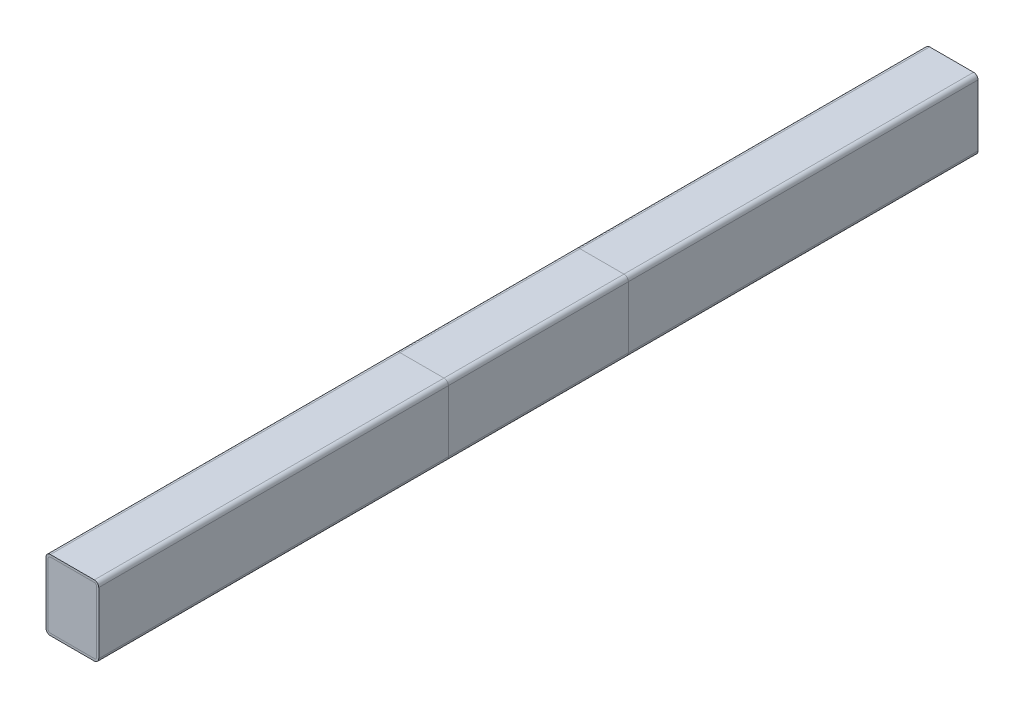
SolidWorks part; units mm, degrees
material "Plain Carbon Steel"
ref_plane "Front Plane" through (0, 0, 0) normal (0, 0, 1) x (1, 0, 0)
ref_plane "Top Plane" through (0, 0, 0) normal (0, 1, 0) x (1, 0, 0)
ref_plane "Right Plane" through (0, 0, 0) normal (1, 0, 0) x (0, 0, -1)
sketch "Sketch4" plane through (0, 0, 0) normal (0, 0, 1) x (1, 0, 0)
  line L4 (31.75, -47.6907) -> (-31.75, -47.6907)
  line L5 (34.925, 44.3843) -> (34.925, -44.5157)
  line L6 (-34.925, -44.5157) -> (-34.925, 44.3843)
  line L7 (-31.75, 47.5593) -> (31.75, 47.5593)
  line L8 (31.75, -50.8657) -> (-31.75, -50.8657)
  line L9 (38.1, 44.3843) -> (38.1, -44.5157)
  line L10 (-31.75, 50.7343) -> (31.75, 50.7343)
  line L11 (-38.1, -44.5157) -> (-38.1, 44.3843)
  arc A4 (-34.925, -44.5157) -> (-31.75, -47.6907) centre (-31.75, -44.5157) ccw
  arc A5 (31.75, -47.6907) -> (34.925, -44.5157) centre (31.75, -44.5157) ccw
  arc A6 (34.925, 44.3843) -> (31.75, 47.5593) centre (31.75, 44.3843) ccw
  arc A7 (-31.75, 47.5593) -> (-34.925, 44.3843) centre (-31.75, 44.3843) ccw
  arc A8 (-38.1, -44.5157) -> (-31.75, -50.8657) centre (-31.75, -44.5157) ccw
  arc A9 (31.75, -50.8657) -> (38.1, -44.5157) centre (31.75, -44.5157) ccw
  arc A10 (38.1, 44.3843) -> (31.75, 50.7343) centre (31.75, 44.3843) ccw
  arc A11 (-31.75, 50.7343) -> (-38.1, 44.3843) centre (-31.75, 44.3843) ccw
  dimension "D1" = 3.175
extrude "Boss-Extrude1" add sketch "Sketch4" along normal mid plane 1270 separate body
sketch "Sketch5" plane through (0, 50.7343, 0) normal (0, 1, 0) x (1, 0, 0)
  line L0 (0, 635) -> (0, 130) construction
  line L1 (31.75, 635) -> (-31.75, 635) construction
  line L2 (0, 130) -> (0, -130) construction
  line L3 (0, -130) -> (0, -635) construction
  line L4 (31.75, -635) -> (-31.75, -635) construction
  line L5 (-38.1, 130) -> (38.1, 130)
  line L6 (-38.1, -635) -> (-38.1, 635) construction
  line L7 (38.1, -635) -> (38.1, 635) construction
  line L8 (-38.1, -130) -> (38.1, -130)
  dimension "D1" = 260
split line "Split Line1"
sketch "Sketch6" plane through (0, 0, 0) normal (0, 0, 1) x (1, 0, 0)
  circle A0 centre (0, 0) radius 3.0965
extrude "Boss-Extrude2" add sketch "Sketch6" along normal mid plane 35.814 separate body
sketch "Sketch7" plane through (0, 0, 635) normal (0, 0, 1) x (1, 0, 0)
  line L0 (-31.75, -47.6907) -> (31.75, -47.6907) construction
  line L1 (34.925, -44.5157) -> (34.925, 44.3843) construction
  line L2 (-34.925, 44.3843) -> (-34.925, -44.5157) construction
  line L3 (31.75, 47.5593) -> (-31.75, 47.5593) construction
  line L4 (-31.75, -47.6907) -> (31.75, -47.6907)
  line L5 (34.925, -44.5157) -> (34.925, 44.3843)
  line L6 (-34.925, 44.3843) -> (-34.925, -44.5157)
  line L7 (31.75, 47.5593) -> (-31.75, 47.5593)
  arc A0 (-34.925, -44.5157) -> (-31.75, -47.6907) centre (-31.75, -44.5157) ccw construction
  arc A1 (31.75, -47.6907) -> (34.925, -44.5157) centre (31.75, -44.5157) ccw construction
  arc A2 (34.925, 44.3843) -> (31.75, 47.5593) centre (31.75, 44.3843) ccw construction
  arc A3 (-31.75, 47.5593) -> (-34.925, 44.3843) centre (-31.75, 44.3843) ccw construction
  arc A4 (-34.925, -44.5157) -> (-31.75, -47.6907) centre (-31.75, -44.5157) ccw
  arc A5 (31.75, -47.6907) -> (34.925, -44.5157) centre (31.75, -44.5157) ccw
  arc A6 (34.925, 44.3843) -> (31.75, 47.5593) centre (31.75, 44.3843) ccw
  arc A7 (-31.75, 47.5593) -> (-34.925, 44.3843) centre (-31.75, 44.3843) ccw
extrude "Boss-Extrude3" add sketch "Sketch7" against normal up to surface (1270 mm away) separate body up to face at (0, -0.0657, -635)
equation "\"M5_tap\"=4.2mm       ' Below you can do mesurements as follows: cm, mm, ft, in, m, "
equation "\"M5_clearence\"=5.5mm"
equation "\"M6_tap\"=5mm"
equation "\"M6_clearence\"=6.6mm"
